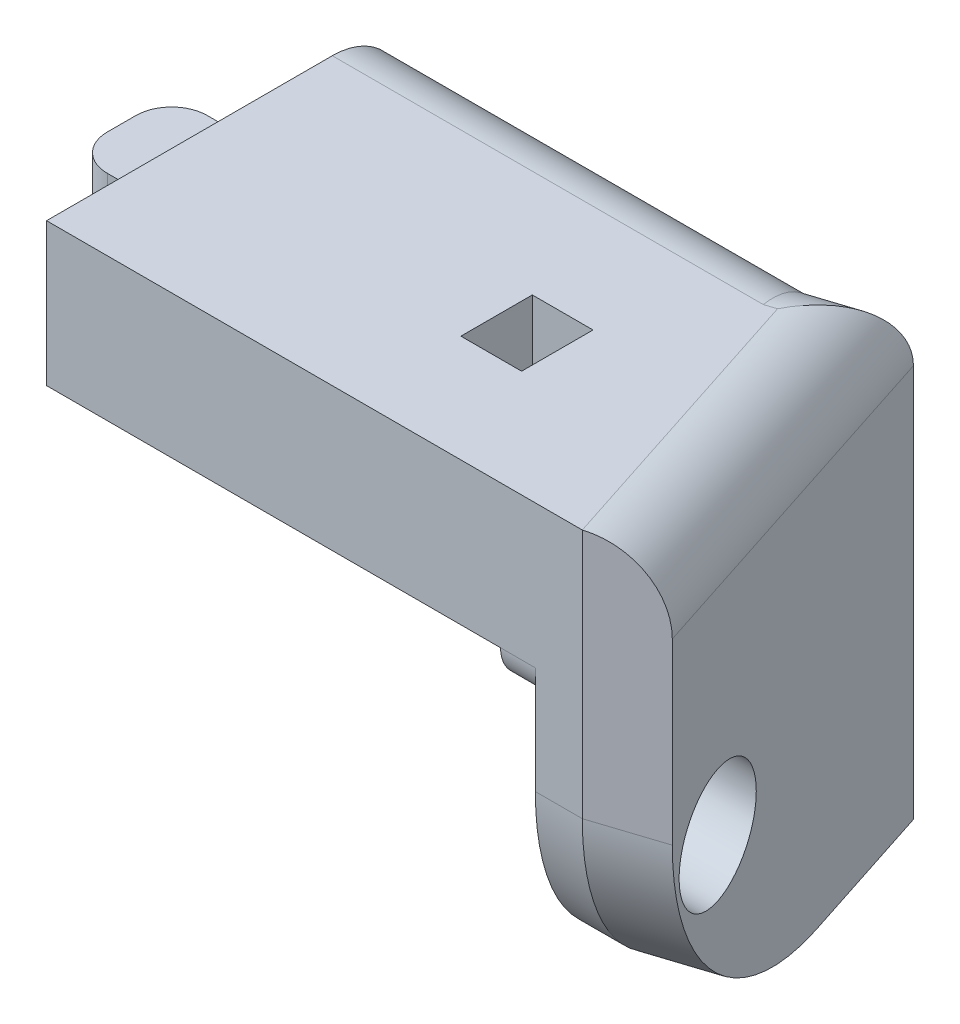
SolidWorks part; units mm, degrees
ref_plane "Front Plane" through (0, 0, 0) normal (0, 0, 1) x (1, 0, 0)
ref_plane "Top Plane" through (0, 0, 0) normal (0, 1, 0) x (1, 0, 0)
ref_plane "Right Plane" through (0, 0, 0) normal (1, 0, 0) x (0, 0, -1)
sketch "Sketch1" plane through (0, 0, 0) normal (0, 1, 0) x (1, 0, 0)
  line L0 (0, 0) -> (-8.253, -25.4)
  line L1 (-8.253, -25.4) -> (67.947, -25.4)
  line L2 (67.947, -25.4) -> (59.6941, 0)
  line L3 (59.6941, 0) -> (0, 0)
  dimension "D1" = 25.4
  dimension "D2" = 108
  dimension "D3" = 76.2
  dimension "D4" = 108
extrude "Boss-Extrude1" add sketch "Sketch1" along normal blind 33.02
sketch "Sketch2" plane through (0, 0, 0) normal (0, -1, 0) x (1, 0, 0)
  line L5 (-3.8829, 22.225) -> (-6.0151, 28.7871)
  line L6 (63.577, 22.225) -> (57.3873, 3.175)
  line L7 (63.577, 22.225) -> (66.5211, 31.286)
  line L8 (2.3068, 3.175) -> (57.3873, 3.175)
  line L9 (57.3873, 3.175) -> (63.577, 22.225)
  line L10 (63.577, 22.225) -> (-3.8829, 22.225)
  line L11 (-3.8829, 22.225) -> (2.3068, 3.175)
  line L15 (-3.8829, 22.225) -> (2.3068, 3.175)
  line L16 (66.5211, 31.286) -> (-6.0151, 28.7871)
  line L17 (57.3873, 3.175) -> (55.1564, -3.6912)
  line L18 (2.3068, 3.175) -> (4.8978, -4.7994)
  line L19 (55.1564, -3.6912) -> (4.8978, -4.7994)
  dimension "D1" = 3.175
extrude "Cut-Extrude1" cut sketch "Sketch2" against normal blind 20.32
fillet "Fillet1" radius 15.24 2 edges at (66.2778, 0, 25.4) (-6.5838, 0, 25.4)
sketch "Sketch4" plane through (0, 33.02, 0) normal (0, 1, 0) x (1, 0, 0)
  line L0 (-8.253, -25.4) -> (67.947, -25.4) construction
  line L1 (51.691, -17.78) -> (56.009, -17.78)
  line L2 (51.691, -17.78) -> (51.691, -12.7)
  line L3 (51.691, -12.7) -> (56.009, -12.7)
  line L4 (56.009, -17.78) -> (56.009, -12.7)
  line L5 (3.685, -17.78) -> (8.003, -17.78)
  line L6 (3.685, -17.78) -> (3.685, -12.7)
  line L7 (3.685, -12.7) -> (8.003, -12.7)
  line L8 (8.003, -17.78) -> (8.003, -12.7)
  dimension "D1" = 4.318
  dimension "D2" = 5.08
  dimension "D3" = 5.08
  dimension "D4" = 4.318
  dimension "D5" = 7.62
  dimension "D6" = 11.938
  dimension "D7" = 11.938
extrude "Cut-Extrude3" cut sketch "Sketch4" against normal blind 20.32
fillet "Fillet2" radius 2.54 1 edges at (29.847, 20.32, 25.4)
sketch "Sketch5" plane through (0, 0, 0) normal (-0.9511, 0, -0.309) x (-0.309, 0, 0.9511)
  line L8 (0, 0) -> (10.6829, 0)
  line L9 (26.7071, 15.24) -> (26.7071, 33.02)
  line L10 (26.7071, 33.02) -> (0, 33.02)
  line L11 (0, 33.02) -> (0, 0)
  line L12 (0, 0) -> (10.6829, 0)
  line L13 (26.7071, 15.24) -> (26.7071, 33.02)
  line L14 (26.7071, 33.02) -> (0, 33.02)
  line L15 (0, 33.02) -> (0, 0)
  ellipse E2 centre (10.6829, 15.24) end of major axis (-5.3414, 15.24) minor radius 15.24 (10.6829, 0) -> (26.7071, 15.24) ccw
  ellipse E3 centre (10.6829, 15.24) end of major axis (-5.3414, 15.24) minor radius 15.24 (10.6829, 0) -> (26.7071, 15.24) ccw
  dimension "D1" = 0
extrude "Boss-Extrude2" add sketch "Sketch5" along normal blind 5.08
sketch "Sketch6" plane through (53.9938, 0, -17.5436) normal (0.9511, 0, -0.309) x (-0.309, 0, -0.9511)
  line L8 (-45.1536, 33.02) -> (-45.1536, 15.24)
  line L9 (-29.1293, 0) -> (-18.4465, 0)
  line L10 (-18.4465, 0) -> (-18.4465, 33.02)
  line L11 (-18.4465, 33.02) -> (-45.1536, 33.02)
  line L12 (-45.1536, 33.02) -> (-45.1536, 15.24)
  line L13 (-29.1293, 0) -> (-18.4465, 0)
  line L14 (-18.4465, 0) -> (-18.4465, 33.02)
  line L15 (-18.4465, 33.02) -> (-45.1536, 33.02)
  ellipse E2 centre (-29.1293, 15.24) end of major axis (-45.1536, 15.24) minor radius 15.24 (-45.1536, 15.24) -> (-29.1293, 0) ccw
  ellipse E3 centre (-29.1293, 15.24) end of major axis (-45.1536, 15.24) minor radius 15.24 (-45.1536, 15.24) -> (-29.1293, 0) ccw
  dimension "D1" = 0
extrude "Boss-Extrude3" add sketch "Sketch6" along normal blind 5.08
sketch "Sketch3" plane through (0, 0, 0) normal (1, 0, 0) x (0, 0, -1)
  line L0 (-22.86, 20.32) -> (0, 20.32) construction
  line L1 (-25.4, 15.24) -> (-25.4, 22.86) construction
  circle A0 centre (-19.05, 12.7) radius 4.064
  dimension "D1" = 8.128
  dimension "D2" = 7.62
  dimension "D3" = 6.35
extrude "Cut-Extrude2" cut sketch "Sketch3" against normal blind 20.32 and the other way blind 88.392
fillet "Fillet3" radius 5.08 5 edges at (-2.4157, 33.02, -0.7849) (62.1098, 33.02, -0.7849) (29.847, 33.02, 0) (-8.9578, 33.02, 11.1302) (68.6519, 33.02, 11.1302)
sketch "Sketch7" plane through (0, 33.02, 0) normal (0, 1, 0) x (1, 0, 0)
  line L0 (-8.253, -25.4) -> (67.947, -25.4) construction
  line L1 (29.847, -25.4) -> (-14.389, -25.4)
  line L2 (29.847, -25.4) -> (29.847, 9.2604)
  line L3 (29.847, 9.2604) -> (-14.389, 9.2604)
  line L4 (-14.389, -25.4) -> (-14.389, 9.2604)
extrude "Cut-Extrude4" cut sketch "Sketch7" against normal blind 37.084
sketch "Sketch8" plane through (29.847, 0, 0) normal (-1, 0, 0) x (0, 0, 1)
  line L0 (25.4, 22.86) -> (25.4, 33.02) construction
  line L1 (18.796, 31.496) -> (11.684, 31.496)
  line L2 (18.796, 31.496) -> (18.796, 27.686)
  line L3 (18.796, 27.686) -> (11.684, 27.686)
  line L4 (11.684, 31.496) -> (11.684, 27.686)
  line L6 (25.4, 33.02) -> (5.08, 33.02) construction
  dimension "D1" = 6.604
  dimension "D2" = 3.81
  dimension "D3" = 1.524
  dimension "D4" = 7.112
extrude "Boss-Extrude4" add sketch "Sketch8" along normal blind 4.826
fillet "Fillet4" radius 2.54 2 edges at (25.021, 29.591, 18.796) (25.021, 29.591, 11.684)
sketch "Sketch9" plane through (0, 20.32, 0) normal (0, -1, 0) x (1, 0, 0)
  line L0 (56.3557, 0) -> (63.7834, 22.86) construction
  line L1 (62.1328, 17.78) -> (29.5755, 17.78)
  line L2 (62.1328, 17.78) -> (62.1328, 25.4)
  line L3 (62.1328, 25.4) -> (29.5755, 25.4)
  line L4 (29.5755, 17.78) -> (29.5755, 25.4)
  line L5 (63.7834, 22.86) -> (29.847, 22.86) construction
  dimension "D1" = 7.62
  dimension "D2" = 5.08
extrude "Cut-Extrude5" cut sketch "Sketch9" against normal blind 2.54
